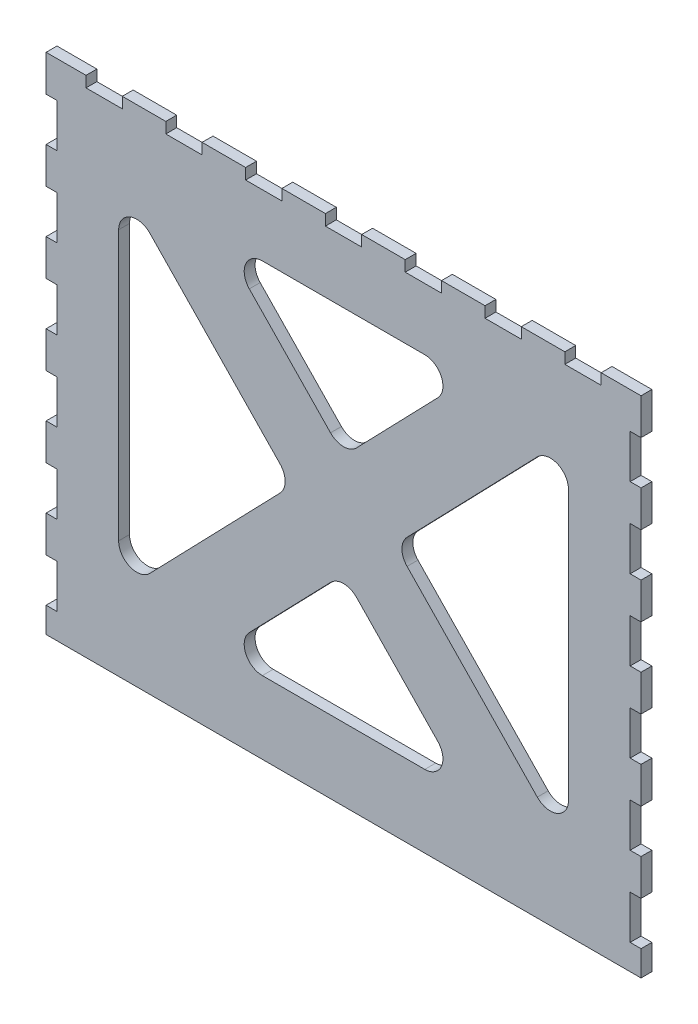
SolidWorks part; units mm, degrees
material "birch 3mm plywood"
ref_plane "Front Plane" through (0, 0, 0) normal (0, 0, 1) x (1, 0, 0)
ref_plane "Top Plane" through (0, 0, 0) normal (0, 1, 0) x (1, 0, 0)
ref_plane "Right Plane" through (0, 0, 0) normal (1, 0, 0) x (0, 0, -1)
sketch "Sketch1" plane through (0, 0, 152) normal (0, 0, 1) x (1, 0, 0)
  line L1 (-82, 69.5) -> (82, 69.5)
  line L2 (-82, 69.5) -> (-82, -69.5)
  line L3 (-82, -69.5) -> (82, -69.5)
  line L4 (82, 69.5) -> (82, -69.5)
  line L6 (-62, -37.1347) -> (-62, 37.1347)
  line L7 (-53.4053, 40.61) -> (-17.504, 3.4753)
  line L12 (75, -62.5) -> (-75, -62.5) construction
  line L13 (75, 62.5) -> (75, -62.5) construction
  line L14 (-75, -62.5) -> (-75, 62.5) construction
  line L15 (-75, 62.5) -> (75, 62.5) construction
  line L18 (22.3929, 49.5) -> (-22.3929, 49.5)
  line L19 (-17.504, -3.4753) -> (-53.4053, -40.61)
  line L20 (-25.9877, 41.0247) -> (-3.5947, 17.8624)
  line L21 (3.5947, 17.8624) -> (25.9877, 41.0247)
  line L23 (53.4053, 40.61) -> (17.504, 3.4753)
  line L24 (62, -37.1347) -> (62, 37.1347)
  line L25 (17.504, -3.4753) -> (53.4053, -40.61)
  line L26 (-75, 0) -> (75, 0) construction
  line L27 (-25.9877, -41.0247) -> (-3.5947, -17.8624)
  line L28 (22.3929, -49.5) -> (-22.3929, -49.5)
  line L29 (3.5947, -17.8624) -> (25.9877, -41.0247)
  line L30 (0, 14.1442) -> (0, -14.1442) construction
  line L31 (-14.1442, 0) -> (14.1442, 0) construction
  line L32 (0, 14.1442) -> (0, -14.1442) construction
  arc A0 (-53.4053, -40.61) -> (-62, -37.1347) centre (-57, -37.1347) cw
  arc A1 (-17.504, -3.4753) -> (-17.504, 3.4753) centre (-21.0988, 0) ccw
  arc A2 (-53.4053, 40.61) -> (-62, 37.1347) centre (-57, 37.1347) ccw
  arc A3 (25.9877, -41.0247) -> (22.3929, -49.5) centre (22.3929, -44.5) cw
  arc A4 (-25.9877, -41.0247) -> (-22.3929, -49.5) centre (-22.3929, -44.5) ccw
  arc A5 (-3.5947, -17.8624) -> (3.5947, -17.8624) centre (0, -21.3377) cw
  arc A6 (17.504, 3.4753) -> (17.504, -3.4753) centre (21.0988, 0) ccw
  arc A7 (53.4053, -40.61) -> (62, -37.1347) centre (57, -37.1347) ccw
  arc A8 (62, 37.1347) -> (53.4053, 40.61) centre (57, 37.1347) ccw
  arc A9 (-25.9877, 41.0247) -> (-22.3929, 49.5) centre (-22.3929, 44.5) cw
  arc A10 (25.9877, 41.0247) -> (22.3929, 49.5) centre (22.3929, 44.5) ccw
  arc A11 (3.5947, 17.8624) -> (-3.5947, 17.8624) centre (0, 21.3377) cw
  point P14 (0, 0)
  point P15 (0, 0)
  point P17 (-78, -55.8021)
  point P32 (-62, 49.5)
  point P35 (34.1815, -49.5)
  point P38 (-34.1815, -49.5)
  point P51 (-34.1815, 49.5)
  point P54 (34.1815, 49.5)
  point P58 (71.436, -87.3268)
  point P59 (-80, -66.4971)
  point P60 (-70.3141, -76.1812)
  point P61 (-80, -66.4558)
  point P62 (-78, -72.9155)
  point P63 (-78, 73.4171)
  point P64 (-77.6237, -68.7403)
  point P68 (-74.0459, -71.9347)
  point P70 (-74.6267, -80.6469)
  point P71 (-60, 42.5374)
  point P72 (-80, -90.2736)
  point P73 (80, -87.3812)
  dimension "D9" = 5
  dimension "D10" = 5
  dimension "D2" = 20
  dimension "D3" = 7
  dimension "D4" = 7
  dimension "D5" = 20
  dimension "D6" = 20
  dimension "D7" = 20
  dimension "D8" = 20
  dimension "D11" = 150
  dimension "D12" = 125
  dimension "D13" = 7
extrude "Boss-Extrude1" add sketch "Sketch1" along normal blind 3
sketch "Sketch2" plane through (0, 0, 155) normal (0, 0, 1) x (1, 0, 0)
  line L0 (0, 69.5) -> (0, -69.5) construction
  line L1 (17, 69.5) -> (17, 66.5)
  line L2 (-5, 69.5) -> (5, 69.5)
  line L3 (-5, 69.5) -> (-5, 66.5)
  line L4 (-82, 69.5) -> (-82, -69.5)
  line L5 (-82, -69.5) -> (82, -69.5)
  line L6 (82, -69.5) -> (82, 69.5)
  line L7 (82, 69.5) -> (-82, 69.5)
  line L8 (-82, 69.5) -> (-82, -69.5)
  line L9 (-82, -69.5) -> (82, -69.5)
  line L10 (82, -69.5) -> (82, 69.5)
  line L11 (82, 69.5) -> (-82, 69.5)
  line L12 (-5, 66.5) -> (5, 66.5)
  line L13 (5, 69.5) -> (5, 66.5)
  line L14 (17, 69.5) -> (27, 69.5)
  line L15 (27, 69.5) -> (27, 66.5)
  line L16 (17, 66.5) -> (27, 66.5)
  line L17 (39, 69.5) -> (39, 66.5)
  line L18 (39, 69.5) -> (49, 69.5)
  line L19 (49, 69.5) -> (49, 66.5)
  line L20 (39, 66.5) -> (49, 66.5)
  line L21 (61, 69.5) -> (61, 66.5)
  line L22 (61, 69.5) -> (71, 69.5)
  line L23 (71, 69.5) -> (71, 66.5)
  line L24 (61, 66.5) -> (71, 66.5)
  line L25 (-27, 69.5) -> (-27, 66.5)
  line L26 (-27, 69.5) -> (-17, 69.5)
  line L27 (-17, 69.5) -> (-17, 66.5)
  line L28 (-27, 66.5) -> (-17, 66.5)
  line L29 (-49, 69.5) -> (-49, 66.5)
  line L30 (-49, 69.5) -> (-39, 69.5)
  line L31 (-39, 69.5) -> (-39, 66.5)
  line L32 (-49, 66.5) -> (-39, 66.5)
  line L33 (-71, 69.5) -> (-71, 66.5)
  line L34 (-71, 69.5) -> (-61, 69.5)
  line L35 (-61, 69.5) -> (-61, 66.5)
  line L36 (-71, 66.5) -> (-61, 66.5)
  line L37 (-82, 37.5) -> (-82, 25.5)
  line L38 (-82, 59.5) -> (-79, 59.5)
  line L39 (-82, 59.5) -> (-82, 47.5)
  line L40 (-82, 47.5) -> (-79, 47.5)
  line L41 (-79, 59.5) -> (-79, 47.5)
  line L42 (-82, 37.5) -> (-79, 37.5)
  line L43 (-79, 37.5) -> (-79, 25.5)
  line L44 (-82, 25.5) -> (-79, 25.5)
  line L45 (-82, 15.5) -> (-82, 3.5)
  line L46 (-82, 15.5) -> (-79, 15.5)
  line L47 (-79, 15.5) -> (-79, 3.5)
  line L48 (-82, 3.5) -> (-79, 3.5)
  line L49 (-82, -6.5) -> (-82, -18.5)
  line L50 (-82, -6.5) -> (-79, -6.5)
  line L51 (-79, -6.5) -> (-79, -18.5)
  line L52 (-82, -18.5) -> (-79, -18.5)
  line L53 (-82, -28.5) -> (-82, -40.5)
  line L54 (-82, -28.5) -> (-79, -28.5)
  line L55 (-79, -28.5) -> (-79, -40.5)
  line L56 (-82, -40.5) -> (-79, -40.5)
  line L57 (-82, -50.5) -> (-82, -62.5)
  line L58 (-82, -50.5) -> (-79, -50.5)
  line L59 (-79, -50.5) -> (-79, -62.5)
  line L60 (-82, -62.5) -> (-79, -62.5)
  line L65 (82, -50.5) -> (79, -50.5)
  line L66 (79, -50.5) -> (79, -62.5)
  line L67 (82, -62.5) -> (79, -62.5)
  line L68 (82, -50.5) -> (82, -62.5)
  line L69 (82, -28.5) -> (79, -28.5)
  line L70 (79, -28.5) -> (79, -40.5)
  line L71 (82, -40.5) -> (79, -40.5)
  line L72 (82, -28.5) -> (82, -40.5)
  line L73 (82, -6.5) -> (79, -6.5)
  line L74 (79, -6.5) -> (79, -18.5)
  line L75 (82, -18.5) -> (79, -18.5)
  line L76 (82, -6.5) -> (82, -18.5)
  line L77 (82, 15.5) -> (79, 15.5)
  line L78 (79, 15.5) -> (79, 3.5)
  line L79 (82, 3.5) -> (79, 3.5)
  line L80 (82, 15.5) -> (82, 3.5)
  line L81 (82, 37.5) -> (79, 37.5)
  line L82 (79, 37.5) -> (79, 25.5)
  line L83 (82, 25.5) -> (79, 25.5)
  line L84 (82, 37.5) -> (82, 25.5)
  line L85 (82, 47.5) -> (79, 47.5)
  line L86 (79, 59.5) -> (79, 47.5)
  line L87 (82, 59.5) -> (79, 59.5)
  line L88 (82, 59.5) -> (82, 47.5)
  point P10 (0, 66.5)
  line M64 (82, -69.5) -> (82, 69.5)
  line M65 (82, 69.5) -> (-82, 69.5)
  dimension "D2" = 10
  dimension "D3" = 3
  dimension "D6" = 12
  dimension "D7" = 12
  dimension "D8" = 3
  dimension "D9" = 12
  dimension "D10" = 10
  dimension "D12" = 10
  dimension "D1" = 0
  dimension "D4" = 4
  dimension "D5" = 4
  dimension "D11" = 6
extrude "Cut-Extrude1" cut sketch "Sketch2" against normal blind 10 contours L8 L44 L43 L42 | L33 L36 L35 L11 | L29 L32 L31 M65 | L25 L28 L27 L11 | L0 L12 L13 M65 | L0 L11 L3 L12 | L1 L16 L15 L11 | L17 L20 L19 L11 | L21 L24 L23 L11 | L87 L86 L85 M64 | L79 L77 L78 M64 | L75 L10 L73 L74 | L71 L69 L70 M64 | L67 L10 L65 L66 | L41 L40 L39 L38 | L47 L48 L45 L46 | L51 L52 L49 L50 | L55 L56 L53 L54 | L59 L60 L57 L58 | L82 L83 L84 L81 region at (2.5, 68, 155) region at (-2.5, 68, 155) region at (-22, 68, 155) region at (22, 68, 155) region at (80.5, -56.5, 155) region at (-44, 68, 155) region at (44, 68, 155) region at (80.5, -34.5, 155) region at (-66, 68, 155) region at (66, 68, 155) region at (80.5, -12.5, 155) region at (80.5, 53.5, 155) region at (80.5, 9.5, 155) region at (-80.5, 31.5, 155)
